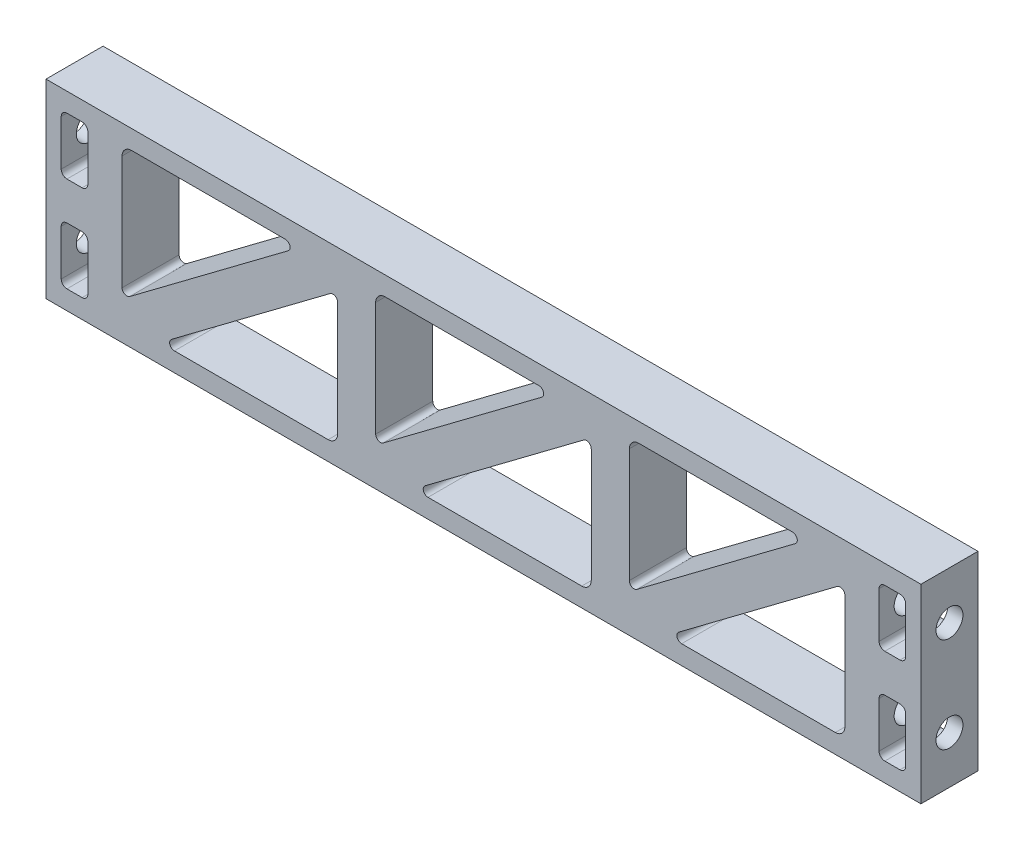
SolidWorks part; units mm, degrees
material "PE High Density"
ref_plane "Front Plane" through (0, 0, 0) normal (0, 0, 1) x (1, 0, 0)
ref_plane "Top Plane" through (0, 0, 0) normal (0, 1, 0) x (1, 0, 0)
ref_plane "Right Plane" through (0, 0, 0) normal (1, 0, 0) x (0, 0, -1)
sketch "Sketch1" plane through (0, 0, 0) normal (0, 0, 1) x (1, 0, 0)
  line L0 (-24.3417, 15.875) -> (-24.3417, -15.875) construction
  line L1 (-73.025, 15.875) -> (73.025, 15.875)
  line L2 (-73.025, 15.875) -> (-73.025, -15.875)
  line L3 (-73.025, -15.875) -> (73.025, -15.875)
  line L4 (73.025, 15.875) -> (73.025, -15.875)
  line L5 (-73.025, 15.875) -> (73.025, -15.875) construction
  line L6 (-73.025, -15.875) -> (73.025, 15.875) construction
  line L7 (24.3417, 15.875) -> (24.3417, -15.875) construction
  line L9 (-69.85, -12.7) -> (-27.5167, 12.7) construction
  line L10 (-69.85, -12.7) -> (-69.85, 12.7) construction
  line L11 (-64.3071, -11.2256) -> (-29.9209, 9.4061)
  line L12 (-73.025, -15.875) -> (-24.3417, -15.875)
  line L13 (-73.025, -15.875) -> (-73.025, 15.875)
  line L14 (-73.025, 15.875) -> (-24.3417, 15.875)
  line L15 (-24.3417, -15.875) -> (-24.3417, 15.875) construction
  line L16 (-69.85, 12.7) -> (-27.5167, 12.7) construction
  line L17 (-27.5167, -12.7) -> (-27.5167, 12.7) construction
  line L18 (-69.85, -12.7) -> (-27.5167, -12.7) construction
  line L19 (-67.4457, -9.4061) -> (-33.0595, 11.2256)
  line L20 (-69.0332, -14.0613) -> (-26.6999, 11.3387) construction
  line L21 (-69.85, -8.0448) -> (-69.85, 11.1125)
  line L22 (-70.6668, -11.3387) -> (-28.3334, 14.0613) construction
  line L23 (-68.2625, 12.7) -> (-33.4679, 12.7)
  line L24 (-63.8988, -12.7) -> (-29.1042, -12.7)
  line L25 (-27.5167, -11.1125) -> (-27.5167, 8.0448)
  line L26 (-15.6238, -11.2256) -> (18.7624, 9.4061)
  line L27 (-18.7624, -9.4061) -> (15.6238, 11.2256)
  line L28 (-21.1667, -8.0448) -> (-21.1667, 11.1125)
  line L29 (-19.5792, 12.7) -> (15.2154, 12.7)
  line L30 (-15.2154, -12.7) -> (19.5792, -12.7)
  line L31 (21.1667, -11.1125) -> (21.1667, 8.0448)
  line L32 (-21.1667, -12.7) -> (21.1667, 12.7) construction
  line L33 (-21.1667, -12.7) -> (-21.1667, 12.7) construction
  line L34 (-21.1667, 12.7) -> (21.1667, 12.7) construction
  line L35 (21.1667, -12.7) -> (21.1667, 12.7) construction
  line L36 (-21.1667, -12.7) -> (21.1667, -12.7) construction
  line L37 (33.0595, -11.2256) -> (67.4457, 9.4061)
  line L38 (29.9209, -9.4061) -> (64.3071, 11.2256)
  line L39 (27.5167, -8.0448) -> (27.5167, 11.1125)
  line L40 (29.1042, 12.7) -> (63.8988, 12.7)
  line L41 (33.4679, -12.7) -> (68.2625, -12.7)
  line L42 (69.85, -11.1125) -> (69.85, 8.0448)
  line L43 (27.5167, -12.7) -> (69.85, 12.7) construction
  line L44 (27.5167, -12.7) -> (27.5167, 12.7) construction
  line L45 (27.5167, 12.7) -> (69.85, 12.7) construction
  line L46 (69.85, -12.7) -> (69.85, 12.7) construction
  line L47 (27.5167, -12.7) -> (69.85, -12.7) construction
  line L59 (-64.3071, -11.2256) -> (-15.6238, -11.2256) construction
  line L60 (-69.85, 15.875) -> (-69.85, -15.875)
  arc A0 (-33.4679, 12.7) -> (-33.0595, 11.2256) centre (-33.4679, 11.9062) cw
  arc A1 (-69.85, -8.0448) -> (-67.4457, -9.4061) centre (-68.2625, -8.0448) ccw
  arc A2 (-69.85, 11.1125) -> (-68.2625, 12.7) centre (-68.2625, 11.1125) cw
  arc A3 (-27.5167, 8.0448) -> (-29.9209, 9.4061) centre (-29.1042, 8.0448) ccw
  arc A4 (-63.8988, -12.7) -> (-64.3071, -11.2256) centre (-63.8988, -11.9062) cw
  arc A5 (-27.5167, -11.1125) -> (-29.1042, -12.7) centre (-29.1042, -11.1125) cw
  arc A6 (15.2154, 12.7) -> (15.6238, 11.2256) centre (15.2154, 11.9062) cw
  arc A7 (-21.1667, -8.0448) -> (-18.7624, -9.4061) centre (-19.5792, -8.0448) ccw
  arc A8 (-21.1667, 11.1125) -> (-19.5792, 12.7) centre (-19.5792, 11.1125) cw
  arc A9 (21.1667, 8.0448) -> (18.7624, 9.4061) centre (19.5792, 8.0448) ccw
  arc A10 (-15.2154, -12.7) -> (-15.6238, -11.2256) centre (-15.2154, -11.9062) cw
  arc A11 (21.1667, -11.1125) -> (19.5792, -12.7) centre (19.5792, -11.1125) cw
  arc A12 (63.8988, 12.7) -> (64.3071, 11.2256) centre (63.8988, 11.9062) cw
  arc A13 (27.5167, -8.0448) -> (29.9209, -9.4061) centre (29.1042, -8.0448) ccw
  arc A14 (27.5167, 11.1125) -> (29.1042, 12.7) centre (29.1042, 11.1125) cw
  arc A15 (69.85, 8.0448) -> (67.4457, 9.4061) centre (68.2625, 8.0448) ccw
  arc A16 (33.4679, -12.7) -> (33.0595, -11.2256) centre (33.4679, -11.9062) cw
  arc A17 (69.85, -11.1125) -> (68.2625, -12.7) centre (68.2625, -11.1125) cw
  point P0 (0, 0)
  point P26 (-30.6022, 12.7)
  point P29 (-69.85, -10.8487)
  point P35 (-27.5167, 10.8487)
  point P38 (-66.7645, -12.7)
  dimension "D7" = 0.7937
  dimension "D8" = 1.5875
  dimension "D9" = 1.5875
  dimension "D10" = 1.5875
  dimension "D11" = 0.7937
  dimension "D12" = 1.5875
  dimension "D1" = 31.75
  dimension "CrossBraceLength" = 146.05
  dimension "D4" = 48.6833
  dimension "D14" = 48.6833
  dimension "D6" = 3.175
  dimension "D2" = 1.5875
  dimension "D5" = 1.5875
  dimension "D3" = 3
  dimension "D13" = 3
extrude "Boss-Extrude1" [suppressed] add sketch "Sketch1" along normal blind 9.525
sketch "Sketch2" plane through (0, 0, 0) normal (0, 0, 1) x (1, 0, 0)
  line L0 (-63.5, 15.875) -> (-63.5, -15.875) construction
  line L1 (-73.025, 15.875) -> (73.025, 15.875)
  line L2 (-73.025, 15.875) -> (-73.025, -15.875)
  line L3 (-73.025, -15.875) -> (73.025, -15.875)
  line L4 (73.025, 15.875) -> (73.025, -15.875)
  line L5 (-73.025, 15.875) -> (73.025, -15.875) construction
  line L6 (-73.025, -15.875) -> (73.025, 15.875) construction
  line L7 (63.5, 15.875) -> (63.5, -15.875) construction
  line L8 (-63.5, -15.875) -> (-63.5, 15.875) construction
  line L9 (-21.1667, -15.875) -> (-21.1667, 15.875) construction
  line L10 (21.1667, -15.875) -> (21.1667, 15.875) construction
  line L11 (-73.025, 0) -> (73.025, 0) construction
  line L12 (-63.5, -15.875) -> (-21.1667, -15.875) construction
  line L13 (-63.5, -15.875) -> (-21.1667, 15.875) construction
  line L14 (-63.5, -15.875) -> (-63.5, 15.875) construction
  line L15 (-63.5, 15.875) -> (-21.1667, 15.875)
  line L16 (-58.7375, 12.7) -> (-33.0729, 12.7)
  line L17 (-59.055, -8.5725) -> (-32.5967, 11.2713)
  line L18 (-60.325, -7.9375) -> (-60.325, 11.1125)
  line L19 (-60.325, 12.7) -> (-30.6917, 12.7) construction
  line L20 (-60.325, -9.525) -> (-30.6917, 12.7) construction
  line L21 (-60.325, -9.525) -> (-60.325, 12.7) construction
  line L22 (-63.5, -15.875) -> (-21.1667, -15.875)
  line L23 (-21.1667, -15.875) -> (-21.1667, 15.875) construction
  line L24 (-51.5938, -12.7) -> (-25.9292, -12.7)
  line L25 (-24.3417, -11.1125) -> (-24.3417, 7.9375)
  line L26 (-52.07, -11.2713) -> (-25.6117, 8.5725)
  line L27 (-53.975, -12.7) -> (-24.3417, 9.525) construction
  line L28 (-24.3417, -12.7) -> (-24.3417, 9.525) construction
  line L29 (-53.975, -12.7) -> (-24.3417, -12.7) construction
  line L30 (17.9917, -11.1125) -> (17.9917, 7.9375)
  line L31 (-9.2604, -12.7) -> (16.4042, -12.7)
  line L32 (-9.7367, -11.2713) -> (16.7217, 8.5725)
  line L33 (-16.7217, -8.5725) -> (9.7367, 11.2713)
  line L34 (-16.4042, 12.7) -> (9.2604, 12.7)
  line L35 (-17.9917, -7.9375) -> (-17.9917, 11.1125)
  line L36 (60.325, -11.1125) -> (60.325, 7.9375)
  line L37 (33.0729, -12.7) -> (58.7375, -12.7)
  line L38 (32.5967, -11.2713) -> (59.055, 8.5725)
  line L39 (25.6117, -8.5725) -> (52.07, 11.2713)
  line L40 (25.9292, 12.7) -> (51.5937, 12.7)
  line L41 (24.3417, -7.9375) -> (24.3417, 11.1125)
  line L48 (-24.3417, -11.1125) -> (17.9917, -11.1125) construction
  line L61 (-69.5325, 12.7) -> (-66.9925, 12.7)
  line L62 (-70.485, 11.7475) -> (-70.485, 4.1275)
  line L63 (-69.5325, 3.175) -> (-66.9925, 3.175)
  line L64 (-66.04, 11.7475) -> (-66.04, 4.1275)
  line L65 (-70.485, 12.7) -> (-66.04, 3.175) construction
  line L66 (-70.485, 3.175) -> (-66.04, 12.7) construction
  line L67 (-68.2625, 15.875) -> (-68.2625, -15.875) construction
  line L68 (-68.2625, 3.175) -> (-68.2625, 11.967) construction
  line L69 (-70.485, 7.9375) -> (-66.04, 7.9375) construction
  line L70 (-70.485, -7.9375) -> (-66.04, -7.9375) construction
  line L71 (-68.2625, -3.175) -> (-68.2625, -11.967) construction
  line L72 (-70.485, -3.175) -> (-66.04, -12.7) construction
  line L73 (-70.485, -12.7) -> (-66.04, -3.175) construction
  line L74 (-66.04, -11.7475) -> (-66.04, -4.1275)
  line L75 (-69.5325, -3.175) -> (-66.9925, -3.175)
  line L76 (-70.485, -11.7475) -> (-70.485, -4.1275)
  line L77 (-69.5325, -12.7) -> (-66.9925, -12.7)
  line L78 (0, -15.875) -> (0, 15.875) construction
  line L79 (70.485, -12.7) -> (66.04, -3.175) construction
  line L80 (70.485, -3.175) -> (66.04, -12.7) construction
  line L81 (68.2625, -3.175) -> (68.2625, -11.967) construction
  line L82 (70.485, -7.9375) -> (66.04, -7.9375) construction
  line L83 (70.485, 7.9375) -> (66.04, 7.9375) construction
  line L84 (68.2625, 3.175) -> (68.2625, 11.967) construction
  line L85 (68.2625, 15.875) -> (68.2625, -15.875) construction
  line L86 (70.485, 3.175) -> (66.04, 12.7) construction
  line L87 (70.485, 12.7) -> (66.04, 3.175) construction
  line L88 (69.5325, -12.7) -> (66.9925, -12.7)
  line L89 (70.485, -11.7475) -> (70.485, -4.1275)
  line L90 (69.5325, -3.175) -> (66.9925, -3.175)
  line L91 (66.04, -11.7475) -> (66.04, -4.1275)
  line L92 (66.04, 11.7475) -> (66.04, 4.1275)
  line L93 (69.5325, 3.175) -> (66.9925, 3.175)
  line L94 (70.485, 11.7475) -> (70.485, 4.1275)
  line L95 (69.5325, 12.7) -> (66.9925, 12.7)
  line L96 (73.025, 15.875) -> (73.025, -15.875)
  arc A0 (-33.0729, 12.7) -> (-32.5967, 11.2713) centre (-33.0729, 11.9063) cw
  arc A1 (-60.325, 11.1125) -> (-58.7375, 12.7) centre (-58.7375, 11.1125) cw
  arc A2 (-60.325, -7.9375) -> (-59.055, -8.5725) centre (-59.5313, -7.9375) ccw
  arc A3 (-25.6117, 8.5725) -> (-24.3417, 7.9375) centre (-25.1354, 7.9375) cw
  arc A4 (-25.9292, -12.7) -> (-24.3417, -11.1125) centre (-25.9292, -11.1125) ccw
  arc A5 (-51.5938, -12.7) -> (-52.07, -11.2713) centre (-51.5938, -11.9063) cw
  arc A6 (16.4042, -12.7) -> (17.9917, -11.1125) centre (16.4042, -11.1125) ccw
  arc A7 (-9.2604, -12.7) -> (-9.7367, -11.2713) centre (-9.2604, -11.9063) cw
  arc A8 (16.7217, 8.5725) -> (17.9917, 7.9375) centre (17.1979, 7.9375) cw
  arc A9 (9.2604, 12.7) -> (9.7367, 11.2713) centre (9.2604, 11.9063) cw
  arc A10 (-17.9917, 11.1125) -> (-16.4042, 12.7) centre (-16.4042, 11.1125) cw
  arc A11 (-17.9917, -7.9375) -> (-16.7217, -8.5725) centre (-17.1979, -7.9375) ccw
  arc A12 (58.7375, -12.7) -> (60.325, -11.1125) centre (58.7375, -11.1125) ccw
  arc A13 (33.0729, -12.7) -> (32.5967, -11.2713) centre (33.0729, -11.9063) cw
  arc A14 (59.055, 8.5725) -> (60.325, 7.9375) centre (59.5312, 7.9375) cw
  arc A15 (51.5937, 12.7) -> (52.07, 11.2713) centre (51.5937, 11.9063) cw
  arc A16 (24.3417, 11.1125) -> (25.9292, 12.7) centre (25.9292, 11.1125) cw
  arc A17 (24.3417, -7.9375) -> (25.6117, -8.5725) centre (25.1354, -7.9375) ccw
  arc A36 (-66.9925, 3.175) -> (-66.04, 4.1275) centre (-66.9925, 4.1275) ccw
  arc A37 (-66.9925, 12.7) -> (-66.04, 11.7475) centre (-66.9925, 11.7475) cw
  arc A38 (-69.5325, 3.175) -> (-70.485, 4.1275) centre (-69.5325, 4.1275) cw
  arc A39 (-69.5325, 12.7) -> (-70.485, 11.7475) centre (-69.5325, 11.7475) ccw
  arc A40 (-69.5325, -12.7) -> (-70.485, -11.7475) centre (-69.5325, -11.7475) cw
  arc A41 (-69.5325, -3.175) -> (-70.485, -4.1275) centre (-69.5325, -4.1275) ccw
  arc A42 (-66.9925, -12.7) -> (-66.04, -11.7475) centre (-66.9925, -11.7475) ccw
  arc A43 (-66.9925, -3.175) -> (-66.04, -4.1275) centre (-66.9925, -4.1275) cw
  arc A44 (66.9925, -3.175) -> (66.04, -4.1275) centre (66.9925, -4.1275) ccw
  arc A45 (66.9925, -12.7) -> (66.04, -11.7475) centre (66.9925, -11.7475) cw
  arc A46 (69.5325, -3.175) -> (70.485, -4.1275) centre (69.5325, -4.1275) cw
  arc A47 (69.5325, -12.7) -> (70.485, -11.7475) centre (69.5325, -11.7475) ccw
  arc A48 (69.5325, 12.7) -> (70.485, 11.7475) centre (69.5325, 11.7475) cw
  arc A49 (69.5325, 3.175) -> (70.485, 4.1275) centre (69.5325, 4.1275) ccw
  arc A50 (66.9925, 12.7) -> (66.04, 11.7475) centre (66.9925, 11.7475) ccw
  arc A51 (66.9925, 3.175) -> (66.04, 4.1275) centre (66.9925, 4.1275) cw
  point P0 (0, 0)
  point P16 (-68.2625, 7.9375)
  point P124 (-68.2625, -7.9375)
  point P168 (68.2625, -7.9375)
  point P169 (68.2625, 7.9375)
  dimension "D9" = 1.5875
  dimension "D8" = 0.7937
  dimension "D10" = 0.7937
  dimension "D12" = 0.7937
  dimension "D13" = 1.5875
  dimension "D14" = 0.7937
  dimension "D19" = 0.9525
  dimension "D20" = 0.9525
  dimension "D21" = 0.9525
  dimension "D22" = 0.9525
  dimension "D1" = 146.05
  dimension "D2" = 31.75
  dimension "D3" = 9.525
  dimension "D4" = 9.525
  dimension "D6" = 42.3333
  dimension "D15" = 42.3333
  dimension "D17" = 4.445
  dimension "D18" = 9.525
  dimension "D23" = 4.7625
  dimension "D24" = 7.9375
  dimension "D7" = 3.175
  dimension "D11" = 3.175
  dimension "D5" = 3
  dimension "D16" = 3
extrude "Boss-Extrude2" add sketch "Sketch2" along normal blind 9.525 contours L4 L1 L2 L3 A17 L41 A16 L40 A15 L39 A11 L35 A10 L34 A9 L33 A2 L18 A1 L16 A0 L17 L24 A5 L26 A3 L25 A4 L32 A8 L30 A6 L31 A7 region at (0, 0, 0)
sketch "Sketch3" plane through (-73.025, 0, 0) normal (-1, 0, 0) x (0, 0, 1)
  line L0 (9.525, 15.875) -> (0, 15.875) construction
  line L1 (0, 0) -> (9.525, 0) construction
  line L2 (9.525, 15.875) -> (9.525, -15.875) construction
  line L3 (4.7625, -15.875) -> (4.7625, 15.875) construction
  line L4 (9.525, -15.875) -> (0, -15.875) construction
  circle A0 centre (4.7625, 7.9375) radius 2.2479
  point P13 (0, 0)
  dimension "D2" = 4.4958
  dimension "D1" = 7.9375
extrude "Cut-Extrude1" cut sketch "Sketch3" against normal blind 11.1125
mirror "Mirror1" about plane through (0, 0, 0) normal (1, 0, 0) of "Cut-Extrude1" second plane through (0, 0, 0) second plane normal (0, 1, 0)
equation "\"Plate Width\" = 5in"
equation "\"Plate Thickness\" = 0.375in"
equation "\"Num holes\" = 4"
equation "\"Plate Height\" = 1.25in"
equation "\"Top Plate Width\" = 4.5in"
equation "\"Plate Clearance Hole Diameter\" = 0.125in"
equation "\"Plate Tap Hole Diameter\" = 0.116in"
equation "\"Bottom Plate Length\" = 6.5in"
equation "\"CrossBraceLength@Sketch1\" = \"Bottom Plate Length\" - 2 * \"Plate Thickness\""
equation "\"D1@Sketch1\"=\"Plate Height\""
equation "\"num_triangle_holes\" = 3"
equation "\"D3@Sketch1\"=\"num_triangle_holes\""
equation "\"D4@Sketch1\"=( \"Bottom Plate Length\" - 2 * \"Plate Thickness\" ) / \"num_triangle_holes\""
equation "\"BorderThickness\" = 0.125"
equation "\"D6@Sketch1\"=\"BorderThickness\""
equation "\"D2@Sketch1\"=\"BorderThickness\"/2"
equation "\"D9@Sketch1\"=\"BorderThickness\"/2"
equation "\"D8@Sketch1\"=\"BorderThickness\"/2"
equation "\"D7@Sketch1\"=\"BorderThickness\"/4"
equation "\"D10@Sketch1\"=\"BorderThickness\"/2"
equation "\"D11@Sketch1\"=\"BorderThickness\"/4"
equation "\"D12@Sketch1\"=\"BorderThickness\"/2"
equation "\"D13@Sketch1\"=\"num_triangle_holes\""
equation "\"D14@Sketch1\"=( \"Bottom Plate Length\" - 2 * \"Plate Thickness\" ) / \"num_triangle_holes\""
equation "\"D1@Boss-Extrude1\"=\"Plate Thickness\""
equation "\"D1@Sketch2\"=\"Bottom Plate Length\" - 2 * \"Plate Thickness\""
equation "\"D2@Sketch2\"=\"Plate Height\""
equation "\"wall_thickness\" = 0.375"
equation "\"D3@Sketch2\"=\"wall_thickness\""
equation "\"D4@Sketch2\"=\"wall_thickness\""
equation "\"D5@Sketch2\"=\"num_triangle_holes\""
equation "\"D6@Sketch2\"=( \"Bottom Plate Length\" - 2 * \"Plate Thickness\" - 2 * \"wall_thickness\" ) / \"num_triangle_holes\" "
equation "\"D7@Sketch2\"=\"BorderThickness\""
equation "\"D8@Sketch2\"=\"BorderThickness\" / 4"
equation "\"D10@Sketch2\"=\"BorderThickness\" / 4"
equation "\"D11@Sketch2\"=\"BorderThickness\""
equation "\"D9@Sketch2\"=\"BorderThickness\"/2"
equation "\"D13@Sketch2\"=\"BorderThickness\"/2"
equation "\"D14@Sketch2\"=\"BorderThickness\"/4"
equation "\"D12@Sketch2\"=\"BorderThickness\"/4"
equation "\"D15@Sketch2\"=( \"Bottom Plate Length\" - 2 * \"Plate Thickness\" - 2 * \"wall_thickness\" ) / \"num_triangle_holes\""
equation "\"D1@Boss-Extrude2\"=\"Plate Thickness\""
equation "\"D16@Sketch2\"=\"num_triangle_holes\""
equation "\"D23@Sketch2\"=\"wall_thickness\"/2"
equation "\"D24@Sketch2\"=\"Plate Height\"/4"
equation "\"Number Eight Clearance Size\" = 0.177in"
equation "\"D1@Sketch3\"=\"Plate Height\" / 4"
equation "\"D2@Sketch3\"=\"Number Eight Clearance Size\""
equation "\"D1@Cut-Extrude1\"=(0.75 - \"Plate Thickness\") + 0.0625"
